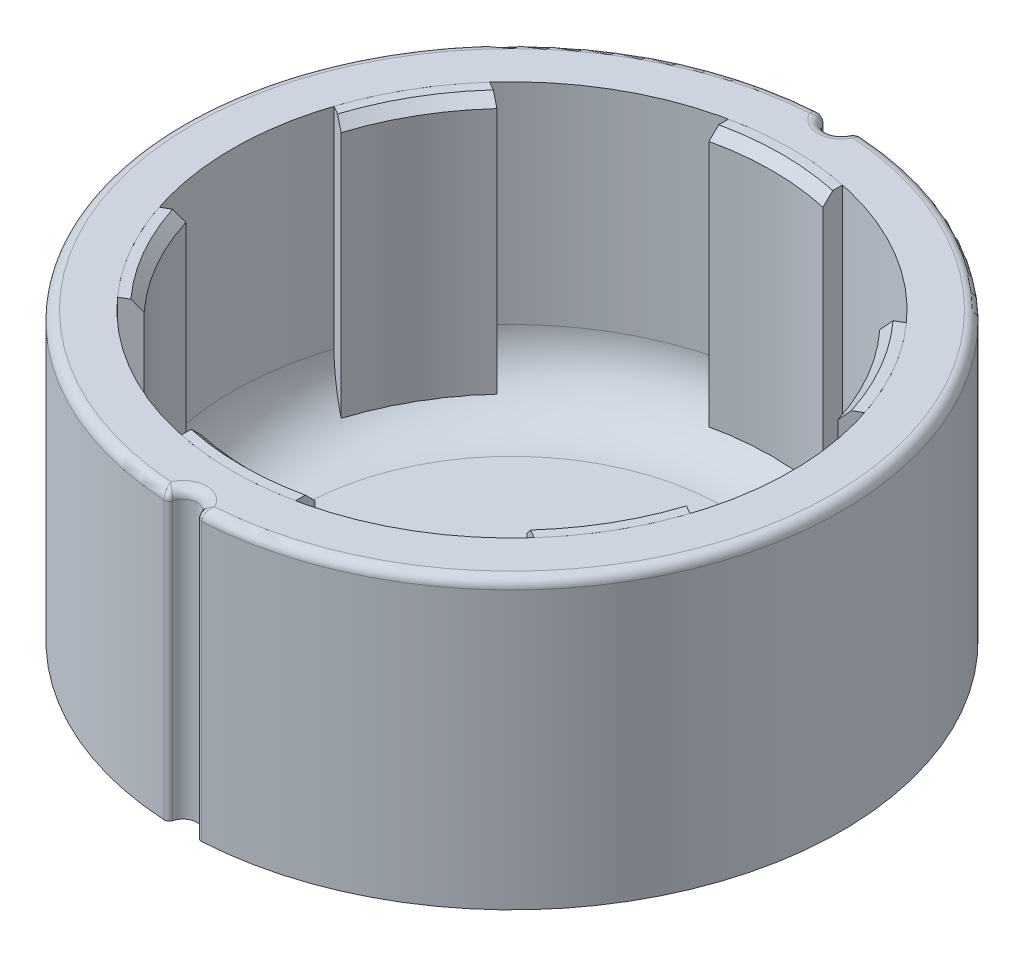
SolidWorks part; units mm, degrees
other "Markup1"
sketch "Sketch4"
other "Markup5"
sketch "Sketch8" plane through (34.5, 25, 34.4428) normal (0.0041, 0.9851, 0.1719) x (0.981, -0.0374, 0.1906)
other "Markup6"
sketch "Sketch9" plane through (34.5, 25, 34.4428) normal (0.0041, 0.9851, 0.1719) x (0.981, -0.0374, 0.1906)
other "Markup7"
sketch "Sketch10" plane through (-34.5, 25, 34.4428) normal (-0.125, 0.9874, 0.0969) x (0.5933, -0.0039, 0.805)
ref_plane "Front Plane" through (0, 0, 0) normal (0, 0, 1) x (1, 0, 0)
ref_plane "Top Plane" through (0, 0, 0) normal (0, 1, 0) x (1, 0, 0)
ref_plane "Right Plane" through (0, 0, 0) normal (1, 0, 0) x (0, 0, -1)
sketch "Sketch1" plane through (0, 0, 0) normal (0, 1, 0) x (1, 0, 0)
  line L3 (0, 0.002) -> (0, 3.7877) construction
  line L4 (0, 3.7877) -> (2.417, 3.7877)
  line L5 (0, 3.7877) -> (-2.417, 3.7877)
  arc A0 (1.9642, -34.442) -> (34.1982, 4.5552) centre (0, 0.002) ccw
  arc A2 (-2.417, 3.7877) -> (2.417, 3.7877) centre (0, 0.002) ccw
  circle A3 centre (0, 0.002) radius 34.5 construction
  arc A7 (-1.3541, 33.8562) -> (1.3541, 33.8562) centre (0, 34.5015) ccw
  arc A8 (34.1982, 4.5552) -> (2.3241, 34.4236) centre (0, 0.002) ccw
  arc A9 (-2.3241, 34.4236) -> (-34.1982, 4.5552) centre (0, 0.002) ccw
  arc A10 (-34.1982, 4.5552) -> (-1.9642, -34.442) centre (0, 0.002) ccw
  arc A11 (1.3541, 33.8562) -> (2.3241, 34.4236) centre (2.2568, 33.4259) cw
  arc A12 (-1.3541, 33.8562) -> (-2.3241, 34.4236) centre (-2.2568, 33.4259) ccw
  arc A13 (1.4518, -34.0686) -> (-1.4518, -34.0686) centre (0, -34.4457) ccw
  arc A14 (1.4518, -34.0686) -> (1.9642, -34.442) centre (1.9358, -33.9428) ccw
  arc A15 (-1.4518, -34.0686) -> (-1.9642, -34.442) centre (-1.9358, -33.9428) cw
  point P15 (1.4997, 34.4694)
  dimension "D2" = 4.834
  dimension "D3" = 4.4915
  dimension "D4" = 34.5
  dimension "D5" = 1
  dimension "D6" = 1.5
  dimension "D7" = 0.5
  dimension "D11" = 1.4997
sketch "Sketch2" plane through (0, 0, 0) normal (0, 1, 0) x (1, 0, 0)
  line L0 (0, 29.25) -> (0, 27.25) construction
  line L1 (-5.9684, 28.6346) -> (0, 29.25) construction
  line L2 (0, 29.25) -> (5.9684, 28.6346) construction
  line L3 (-5.9684, 28.6346) -> (-5.9684, 26.5884)
  line L6 (5.9684, 26.5884) -> (5.9684, 28.6346)
  circle A16 centre (0, 0) radius 29.25
  arc A18 (-5.9684, 26.5884) -> (5.9684, 26.5884) centre (0, 0) cw
  point P3 (0, 27.25)
  dimension "D1" = 58.5
  dimension "D2" = 6
  dimension "D3" = 2
extrude "Boss-Extrude1" add sketch "Sketch1" along normal blind 30 contours A10 A0 A8 A7 A9 A2 L5 L4 | L5 A2 L4 region at (0, 0, 0.1522) region at (2.2155, 0, 33.5591)
extrude "Cut-Extrude2" cut sketch "Sketch2" along normal up to next from offset 1 contours A16 | A16 region at (0, 0, 0.2532)
extrude "Boss-Extrude2" add sketch "Sketch2<2>" along normal up to surface (30 mm away) separate body contours A16 region at (0, 0, -28.0368) up to face at (0, 30, 29.25)
sketch "Sketch2<2>" plane through (0, 0, 0) normal (0, 1, 0) x (1, 0, 0) same geometry as "Sketch2"
chamfer "Chamfer2" distance 1 angle 45 1 edges at (0, 30, -27.25)
pattern_circular "CirPattern2" count 6 over 360 about axis through (0, 30, 0) along (0, 1, 0) of bodies 106
fillet "Fillet1" radius 1 8 edges at (-1.7518, 30, -34.2891) (0, 30, -33.0015) (1.7518, 30, -34.2891) (34.4995, 30, 0.1783) (1.6412, 30, 34.3469) (0, 30, 32.9457) (-1.6412, 30, 34.3469) (-34.4995, 30, 0.1783)
fillet "Fillet2" radius 7 1 edges at (0, 1, 29.25)
